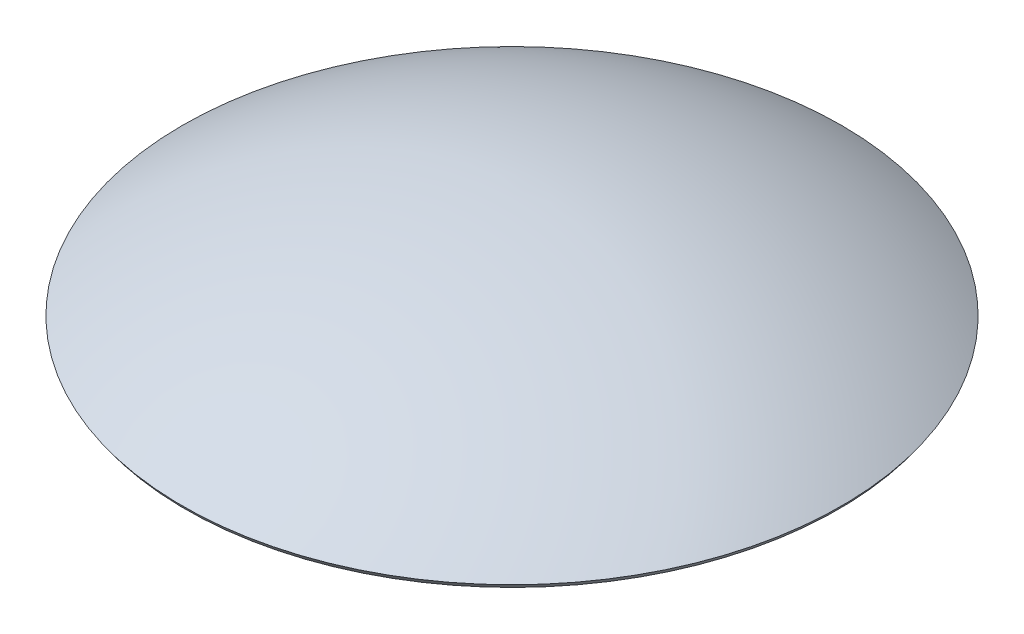
SolidWorks part; units mm, degrees
ref_plane "Front Plane" through (0, 0, 0) normal (0, 0, 1) x (1, 0, 0)
ref_plane "Top Plane" through (0, 0, 0) normal (0, 1, 0) x (1, 0, 0)
ref_plane "Right Plane" through (0, 0, 0) normal (1, 0, 0) x (0, 0, -1)
sketch "Sketch1" plane through (0, 0, 0) normal (0, 0, 1) x (1, 0, 0)
  line L0 (0, 0) -> (0, 294.7292)
  line L1 (0, 0) -> (-150.9529, 261.458)
  line L2 (0, 0) -> (-176.9973, 252.7783)
  circle A0 centre (0, 0) radius 250
  circle A1 centre (0, 0) radius 247.5
  circle A2 centre (0, 0) radius 245
  dimension "D1" = 500
  dimension "D2" = 495
  dimension "D3" = 490
  dimension "D4" = 30
  dimension "D5" = 5
revolve "Revolve1" add sketch "Sketch1" angle 360 about L0 region at (-63.7437, 237.8949, 0) region at (-64.3941, 240.3222, 0) region at (-133.612, 209.7288, 0)
